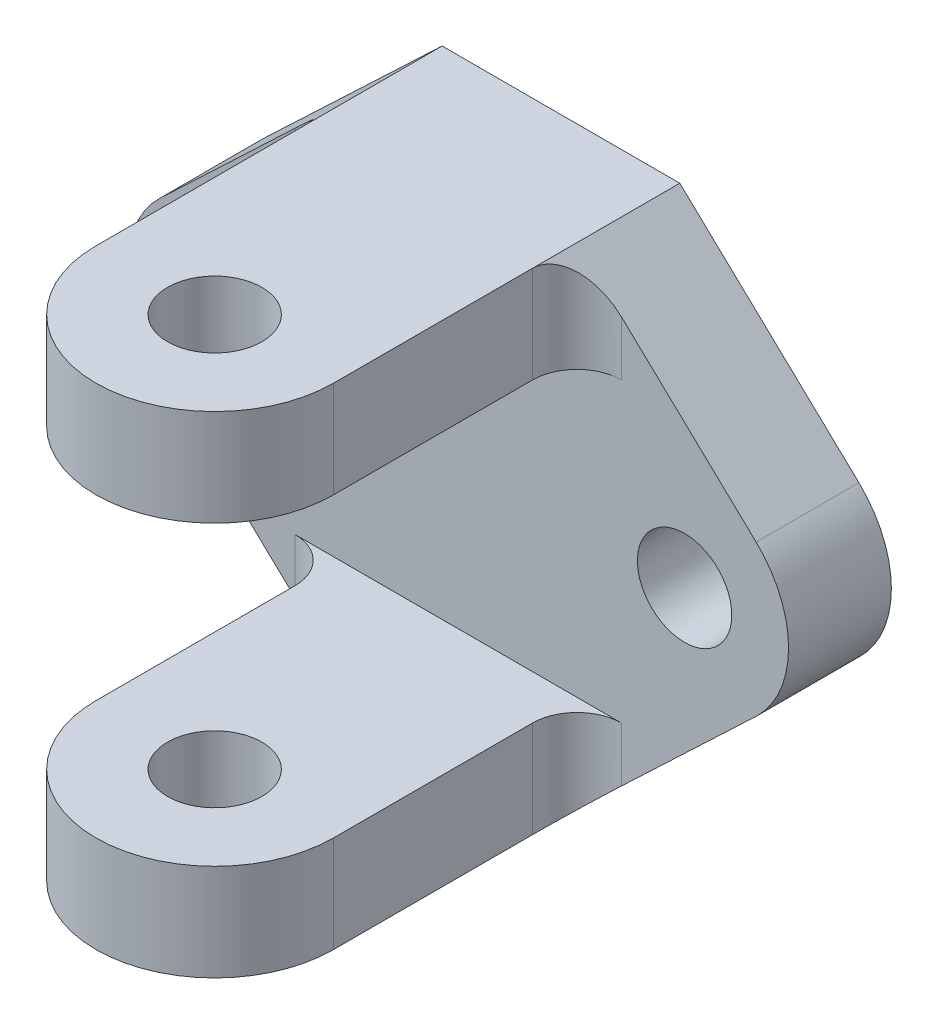
SolidWorks part; units mm, degrees
material "7075-T6 (SN)"
ref_plane "Front Plane" through (0, 0, 0) normal (0, 0, 1) x (1, 0, 0)
ref_plane "Top Plane" through (0, 0, 0) normal (0, 1, 0) x (1, 0, 0)
ref_plane "Right Plane" through (0, 0, 0) normal (1, 0, 0) x (0, 0, -1)
sketch "Sketch1" plane through (0, 0, 0) normal (0, 0, 1) x (1, 0, 0)
  line L0 (15.24, 0) -> (-15.24, 0) construction
  line L1 (-23.24, -16.51) -> (23.24, -16.51)
  line L2 (-23.24, -16.51) -> (-23.24, 16.51)
  line L3 (-23.24, 16.51) -> (23.24, 16.51)
  line L4 (23.24, -16.51) -> (23.24, 16.51)
  line L5 (-23.24, -16.51) -> (23.24, 16.51) construction
  line L6 (-23.24, 16.51) -> (23.24, -16.51) construction
  circle A0 centre (15.24, 0) radius 3.175
  circle A1 centre (-15.24, 0) radius 3.175
  point P0 (0, 0)
  dimension "D1" = 6.35
  dimension "D2" = 30.48
  dimension "D3" = 8
  dimension "D4" = 16.51
extrude "Boss-Extrude1" add sketch "Sketch1" along normal blind 9.46
sketch "Sketch2" plane through (0, 0, 9.46) normal (0, 0, 1) x (1, 0, 0)
  line L0 (-15.24, 0) -> (15.24, 0) construction
  line L2 (-23.24, 10) -> (23.24, 10)
  line L3 (-23.24, 10) -> (-23.24, 16.51)
  line L4 (-23.24, 16.51) -> (23.24, 16.51)
  line L5 (23.24, 10) -> (23.24, 16.51)
  line L6 (-23.24, 10) -> (23.24, 16.51) construction
  line L7 (-23.24, 16.51) -> (23.24, 10) construction
  line L8 (-23.24, 16.51) -> (-23.24, -16.51) construction
  line L9 (23.24, -10) -> (23.24, -16.51)
  line L10 (-23.24, -10) -> (-23.24, -16.51)
  line L11 (-23.24, -16.51) -> (23.24, -10) construction
  line L12 (-23.24, -10) -> (23.24, -16.51) construction
  line L13 (-23.24, -10) -> (23.24, -10)
  line L14 (-23.24, -16.51) -> (23.24, -16.51)
  circle A0 centre (-15.24, 0) radius 3.175 construction
  circle A1 centre (15.24, 0) radius 3.175 construction
  point P6 (0, 13.255)
  point P21 (0, -13.255)
  dimension "D1" = 20
extrude "Boss-Extrude2" add sketch "Sketch2" along normal blind 53
sketch "Sketch3" plane through (0, 0, 0) normal (0, 1, 0) x (1, 0, 0)
  point P0 (0, -25.8481)
  dimension "D1" = 25.8481
ref_point "UBJ Point"
sketch "Sketch4" plane through (0, 0, 0) normal (0, 1, 0) x (1, 0, 0)
  circle A0 centre (0, -25.8481) radius 3.175
  dimension "D1" = 6.35
extrude "Cut-Extrude1" cut sketch "Sketch4" against normal up to surface and the other way up to surface up to face at (0, -16.51, 31.23) other way up to face at (0, 16.51, 31.23)
sketch "Sketch5" plane through (0, 0, 0) normal (0, 1, 0) x (1, 0, 0)
  line L0 (23.24, -9.46) -> (7.424, -31.2394)
  line L1 (-7.424, -31.2394) -> (-23.24, -9.46)
  line L4 (23.24, 0) -> (-23.24, 0)
  line L5 (-23.24, 0) -> (-23.24, -62.46)
  line L6 (-23.24, -62.46) -> (23.24, -62.46)
  line L7 (23.24, -62.46) -> (23.24, 0)
  line L9 (-23.24, -9.46) -> (-23.24, -62.46)
  line L10 (-23.24, -62.46) -> (23.24, -62.46)
  line L11 (23.24, -62.46) -> (23.24, -9.46)
  line L12 (23.24, -9.46) -> (-23.24, -9.46)
  line L13 (23.24, -62.46) -> (23.24, -9.46)
  line L14 (-23.24, -62.46) -> (23.24, -62.46)
  line L15 (-23.24, -9.46) -> (-23.24, -62.46)
  line L17 (23.24, -62.46) -> (23.24, -9.46)
  line L18 (-23.24, -62.46) -> (23.24, -62.46)
  line L19 (-23.24, -9.46) -> (-23.24, -62.46)
  arc A0 (-7.424, -31.2394) -> (7.424, -31.2394) centre (0, -25.8481) ccw
  circle A1 centre (0, -25.8481) radius 3.175 construction
  circle A2 centre (0, -25.8481) radius 3.175 construction
  dimension "D3" = 6
  dimension "D1" = 0
  dimension "D2" = 0
extrude "Cut-Extrude2" [suppressed] cut sketch "Sketch5" against normal up to surface and the other way up to surface contours A0 L1 L9 L10 L11 L0 up to face at (0, -16.51, 29.0231) other way up to face at (0, 16.51, 22.6731)
sketch "Sketch6" plane through (0, 0, 0) normal (0, 1, 0) x (1, 0, 0)
  line L0 (-8, -25.8481) -> (-8, -17.46)
  line L1 (8, -25.8481) -> (8, -17.46)
  line L2 (-16, -9.46) -> (-23.24, -9.46)
  line L3 (-8, -17.46) -> (-8, -9.46)
  line L4 (23.24, -9.46) -> (-23.24, -9.46)
  line L5 (-23.24, -9.46) -> (-23.24, -62.46)
  line L6 (-23.24, -62.46) -> (23.24, -62.46)
  line L7 (23.24, -62.46) -> (23.24, -9.46)
  line L8 (23.24, -9.46) -> (16, -9.46)
  line L9 (-23.24, -9.46) -> (-23.24, -62.46)
  line L10 (-23.24, -62.46) -> (23.24, -62.46)
  line L11 (23.24, -62.46) -> (23.24, -9.46)
  line L12 (-8, -9.46) -> (-16, -9.46)
  line L13 (8, -17.46) -> (8, -9.46)
  line L14 (8, -9.46) -> (16, -9.46)
  arc A0 (-8, -25.8481) -> (8, -25.8481) centre (0, -25.8481) ccw
  circle A1 centre (0, -25.8481) radius 3.175 construction
  arc A2 (-8, -17.46) -> (-16, -9.46) centre (-16, -17.46) ccw construction
  arc A3 (8, -17.46) -> (16, -9.46) centre (16, -17.46) cw construction
  dimension "D2" = 8
  dimension "D3" = 8
  dimension "D1" = 0
extrude "Cut-Extrude3" cut sketch "Sketch6" against normal up to surface and the other way up to surface contours A0 L3 L12 L2 L9 L10 L11 L8 L14 L13 region at (0, 0, 38.5664) up to face at (0, -16.51, 29.0231) other way up to face at (0, 16.51, 22.6731)
fillet "Fillet1" [suppressed] radius 12.7
sketch "Sketch7" plane through (0, 0, 0) normal (0, 0, 1) x (1, 0, 0)
  line L0 (-15.24, 7) -> (-8, 7)
  line L1 (-15.24, -7) -> (-8, -7)
  line L2 (-8, 10) -> (-8, 7)
  line L3 (-8, -10) -> (-8, -7)
  line L4 (0, 10.3988) -> (0, -8.4154) construction
  line L5 (8, -10) -> (8, -7)
  line L6 (8, 10) -> (8, 16.51)
  line L7 (23.24, 16.51) -> (23.24, -16.51)
  line L8 (8, -10) -> (8, -16.51)
  line L9 (8, 10) -> (8, 7)
  line L10 (15.24, 7) -> (8, 7)
  line L11 (15.24, -7) -> (8, -7)
  line L12 (8, 10) -> (-8, 10)
  line L15 (-23.24, 16.51) -> (-23.24, -16.51)
  line L18 (-8, -10) -> (8, -10)
  line L21 (23.24, -16.51) -> (23.24, 16.51)
  line L27 (-23.24, 16.51) -> (-23.24, -16.51)
  line L33 (23.24, -16.51) -> (23.24, 16.51)
  line L36 (-8, 16.51) -> (-8, 10)
  line L37 (-8, -10) -> (-8, -16.51)
  line L48 (-8, 10) -> (-8, 16.51)
  line L49 (-8, -16.51) -> (-8, -10)
  line L52 (-8, 16.51) -> (-23.24, 16.51)
  line L53 (-8, 16.51) -> (-23.24, 16.51)
  line L54 (-23.24, -16.51) -> (-8, -16.51)
  line L55 (-23.24, -16.51) -> (-8, -16.51)
  line L56 (8, -10) -> (8, -16.51)
  line L57 (8, -16.51) -> (23.24, -16.51)
  line L58 (8, -16.51) -> (23.24, -16.51)
  line L59 (23.24, 16.51) -> (8, 16.51)
  line L60 (23.24, 16.51) -> (8, 16.51)
  line L61 (8, 16.51) -> (8, 10)
  arc A0 (-15.24, 7) -> (-15.24, -7) centre (-15.24, 0) ccw
  circle A1 centre (-15.24, 0) radius 3.175 construction
  arc A2 (15.24, 7) -> (15.24, -7) centre (15.24, 0) cw
  dimension "D2" = 7
  dimension "D1" = 0
extrude "Cut-Extrude4" cut sketch "Sketch7" along normal up to surface (9.46 mm away) contours A0 L0 L2 L53 L27 L55 L3 L1 | L10 A2 L11 L5 L7 L9 region at (-22.6037, 0, 0) region at (8.3637, 13.255, 0) up to face at (18.415, 0, 9.46)
fillet "Fillet2" [suppressed] radius 5
sketch "Sketch8" plane through (0, 0, 0) normal (0, 0, 1) x (1, 0, 0)
  line L0 (15.24, 7) -> (8, 7) construction
  line L1 (8, 16.51) -> (8, 7) construction
  line L2 (15.24, 7) -> (8, 7)
  line L3 (8, 16.51) -> (8, 7)
  line L4 (6.7586, 0) -> (-5.803, 0) construction
  line L5 (0, 7.1591) -> (0, -7.1591) construction
  line L6 (8, 16.51) -> (20.0561, 5.0799)
  line L7 (-8, 16.51) -> (-8, 7)
  line L8 (-15.24, 7) -> (-8, 7)
  line L9 (-8, 16.51) -> (-20.0561, 5.0799)
  line L10 (-8, -16.51) -> (-20.0561, -5.0799)
  line L11 (-15.24, -7) -> (-8, -7)
  line L12 (-8, -16.51) -> (-8, -7)
  line L13 (8, -16.51) -> (8, -7)
  line L14 (15.24, -7) -> (8, -7)
  line L15 (8, -16.51) -> (20.0561, -5.0799)
  arc A0 (15.24, -7) -> (15.24, 7) centre (15.24, 0) ccw construction
  arc A1 (20.0561, 5.0799) -> (15.24, 7) centre (15.24, 0) ccw
  arc A2 (-20.0561, 5.0799) -> (-15.24, 7) centre (-15.24, 0) cw
  arc A3 (-20.0561, -5.0799) -> (-15.24, -7) centre (-15.24, 0) ccw
  arc A4 (20.0561, -5.0799) -> (15.24, -7) centre (15.24, 0) cw
extrude "Boss-Extrude3" add sketch "Sketch8" along normal up to surface (9.46 mm away) contours L15 A4 L14 L13 | A3 L10 L12 L11 | L6 A1 L2 L3 | L9 A2 L8 L7 region at (-11.4707, -10.1007, 0) region at (11.4707, -10.1007, 0) up to face at (0, 0, 9.46)
fillet "Fillet3" radius 3 4 edges at (8, 13.255, 9.46) (-8, 13.255, 9.46) (-8, -13.255, 9.46) (8, -13.255, 9.46)
sketch "Sketch10" plane through (0, 0, 0) normal (0, 0, 1) x (1, 0, 0)
  line L5 (-8, 16.51) -> (-20.0561, 5.0799)
  line L6 (-8, 16.51) -> (-20.0561, 5.0799)
  line L7 (8, 16.51) -> (-8, 16.51)
  line L8 (20.0561, 5.0799) -> (8, 16.51)
  line L9 (8, -16.51) -> (20.0561, -5.0799)
  line L10 (-8, -16.51) -> (8, -16.51)
  line L13 (8, 16.51) -> (-8, 16.51)
  line L14 (20.0561, 5.0799) -> (8, 16.51)
  line L15 (8, -16.51) -> (20.0561, -5.0799)
  line L16 (-8, -16.51) -> (8, -16.51)
  line L18 (-20.0561, -5.0799) -> (-8, -16.51)
  line L19 (-20.0561, -5.0799) -> (-8, -16.51)
  arc A2 (-20.0561, 5.0799) -> (-20.0561, -5.0799) centre (-15.24, 0) ccw
  arc A3 (20.0561, -5.0799) -> (20.0561, 5.0799) centre (15.24, 0) ccw
  arc A5 (20.0561, -5.0799) -> (20.0561, 5.0799) centre (15.24, 0) ccw
  arc A6 (-20.0561, 5.0799) -> (-20.0561, -5.0799) centre (-15.24, 0) ccw
  dimension "D1" = 0
extrude "Cut-Extrude5" cut sketch "Sketch10" along normal blind 2.54
